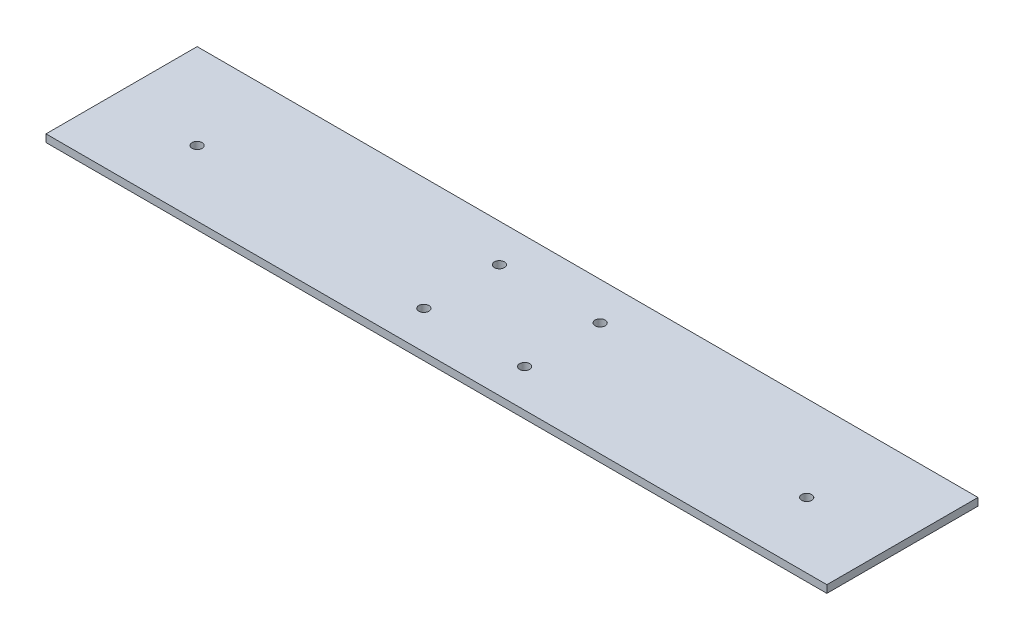
SolidWorks part; units mm, degrees
ref_plane "Płaszczyzna przednia" through (0, 0, 0) normal (0, 0, 1) x (1, 0, 0)
ref_plane "Płaszczyzna górna" through (0, 0, 0) normal (0, 1, 0) x (1, 0, 0)
ref_plane "Płaszczyzna prawa" through (0, 0, 0) normal (1, 0, 0) x (0, 0, -1)
sketch "Sketch1" plane through (0, 0, 0) normal (0, 1, 0) x (1, 0, 0)
  line L1 (-10, 0) -> (300, 0)
  line L2 (-10, 0) -> (-10, 60)
  line L3 (-10, 60) -> (300, 60)
  line L4 (300, 0) -> (300, 60)
  dimension "D1" = 310
  dimension "D2" = 60
extrude "Boss-Extrude1" add sketch "Sketch1" along normal blind 3
hole_wizard "Otwór pod śrubę M41" positions "Sketch2" profile "Sketch3" hole size "M4" standard "Ansi Metric" end condition through all
sketch "Sketch2" plane through (0, 3, 0) normal (0, 1, 0) x (1, 0, 0)
  line L0 (-10, 60) -> (-10, 0) construction
  line L1 (-10, 0) -> (300, 0) construction
  line L2 (300, 0) -> (300, 60) construction
  line L3 (300, 60) -> (-10, 60) construction
  point P0 (266, 26)
  point P2 (24, 26)
  point P20 (125, 15)
  point P22 (165, 15)
  point P24 (165, 45)
  point P26 (125, 45)
  point P37 (0, 0)
  point P38 (0, 0)
  point P39 (0, 0)
  point P40 (0, 0)
  point P41 (0, 0)
  point P42 (0, 0)
  point P43 (0, 0)
  point P44 (0, 0)
  dimension "D1" = 34
  dimension "D3" = 34
  dimension "D4" = 34
  dimension "D11" = 15
  dimension "D12" = 15
  dimension "D15" = 15
  dimension "D16" = 15
  dimension "D25" = 40
  dimension "D26" = 40
  dimension "D27" = 135
  dimension "D28" = 135
  dimension "D29" = 34
sketch "Sketch3" plane through (266, 3, -26) normal (1, 0, 0) x (0, 0, 1)
  line L0 (0, 0) -> (0, 3)
  line L1 (0, 3) -> (2, 3)
  line L2 (2, 3) -> (2, 0)
  line L5 (2, 0) -> (0, 0)
  line L11 (0, -6.35) -> (0, 107.95) construction
  dimension "Œrednica otworu na wylot" = 4
  dimension "G³êbokoœæ otworu na wylot" = 3
